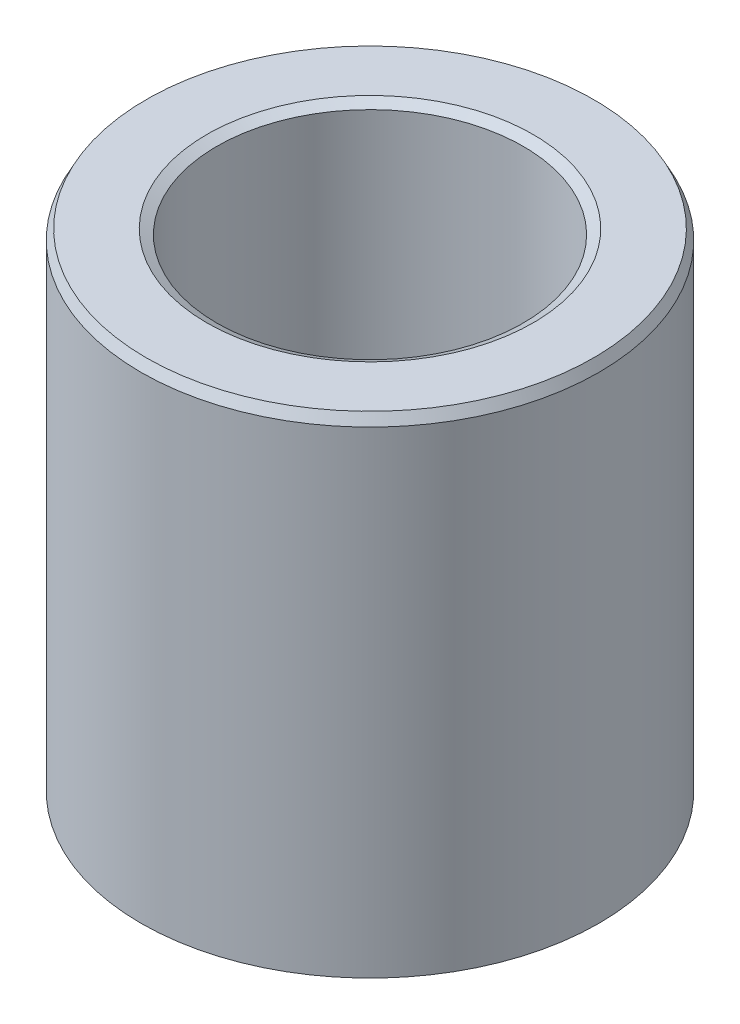
SolidWorks part; units mm, degrees
ref_plane "Front Plane" through (0, 0, 0) normal (0, 0, 1) x (1, 0, 0)
ref_plane "Top Plane" through (0, 0, 0) normal (0, 1, 0) x (1, 0, 0)
ref_plane "Right Plane" through (0, 0, 0) normal (1, 0, 0) x (0, 0, -1)
sketch "Sketch1" plane through (0, 0, 0) normal (0, 1, 0) x (1, 0, 0)
  circle A0 centre (0, 0) radius 50
  dimension "SLEEVE_OD" = 100
extrude "Boss-Extrude1" add sketch "Sketch1" along normal blind 107.5396
sketch "Sketch2" plane through (0, 0, 0) normal (0, 1, 0) x (1, 0, 0)
  circle A0 centre (0, 0) radius 33.4564
  dimension "BORE_D" = 66.9127
extrude "Cut-Extrude1" cut sketch "Sketch2" along normal through all
chamfer "Chamfer1" distance 2.1844 angle 27.529 4 edges at (0, 107.5396, 33.4564) (0, 0, 33.4564) (0, 0, 50) (0, 107.5396, 50) first distance on face at (0, 107.5396, 33.4564) first distance on face at (0, 0, 33.4564) first distance on face at (0, 107.5396, 50)
